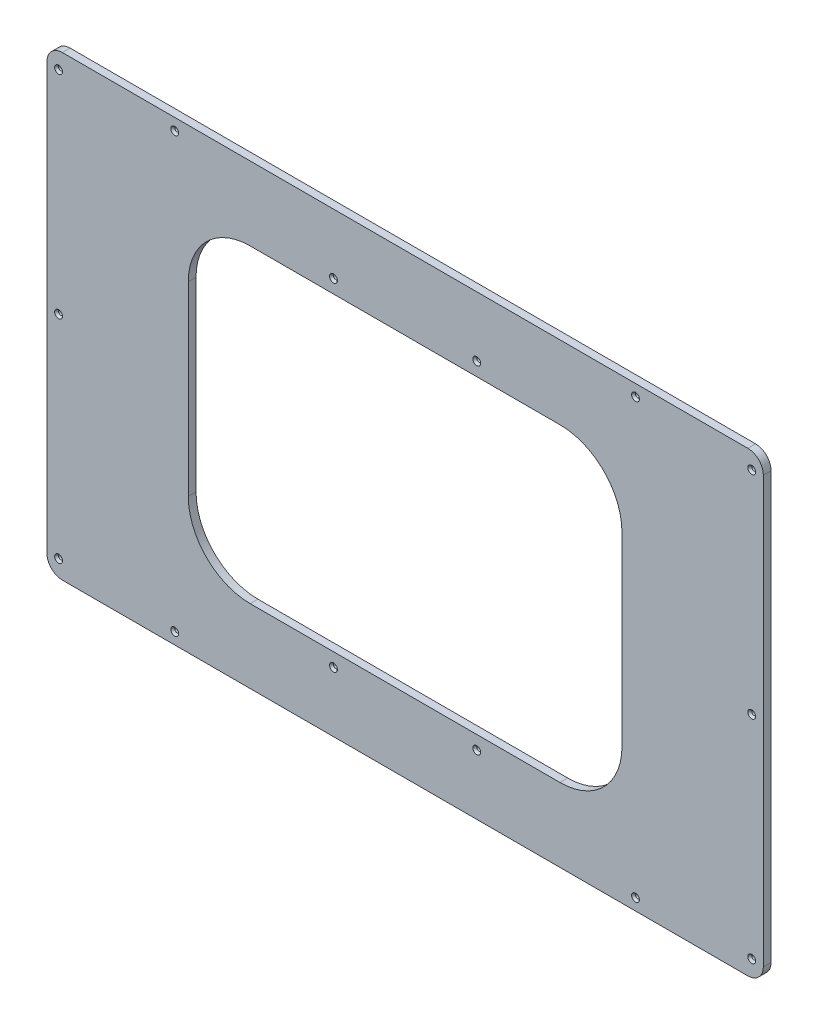
SolidWorks part; units mm, degrees
material "PE High Density"
ref_plane "Front Plane" through (0, 0, 0) normal (0, 0, 1) x (1, 0, 0)
ref_plane "Top Plane" through (0, 0, 0) normal (0, 1, 0) x (1, 0, 0)
ref_plane "Right Plane" through (0, 0, 0) normal (1, 0, 0) x (0, 0, -1)
sketch "Sketch1" plane through (0, 0, 0) normal (0, 0, 1) x (1, 0, 0)
  line L1 (-587.375, 374.65) -> (587.375, 374.65)
  line L2 (-587.375, 374.65) -> (-587.375, -374.65)
  line L3 (-587.375, -374.65) -> (587.375, -374.65)
  line L4 (587.375, 374.65) -> (587.375, -374.65)
  line L5 (-587.375, 374.65) -> (587.375, -374.65) construction
  line L6 (-587.375, -374.65) -> (587.375, 374.65) construction
  line L11 (-355.6, 254) -> (355.6, 254)
  line L12 (-355.6, 254) -> (-355.6, -254)
  line L13 (-355.6, -254) -> (355.6, -254)
  line L14 (355.6, 254) -> (355.6, -254)
  line L15 (-355.6, 254) -> (355.6, -254) construction
  line L16 (-355.6, -254) -> (355.6, 254) construction
  point P0 (0, 0)
  point P6 (0, 0)
  dimension "D1" = 231.775
  dimension "D2" = 749.3
  dimension "D3" = 508
  dimension "D4" = 711.2
extrude "Boss-Extrude1" add sketch "Sketch1" along normal blind 12.7
fillet "Fillet1" radius 101.6 4 edges at (355.6, 254, 6.35) (355.6, -254, 6.35) (-355.6, -254, 6.35) (-355.6, 254, 6.35)
hole_wizard "CSK for 1/4 Flat Head Machine Screw1" positions "Sketch4" profile "Sketch5" countersink size "1/4" standard "ANSI Inch" end condition through all
sketch "Sketch4" plane through (0, 0, 12.7) normal (0, 0, 1) x (1, 0, 0)
  line L0 (-587.375, -374.65) -> (587.375, -374.65) construction
  line L1 (-587.375, 374.65) -> (-587.375, -374.65) construction
  line L2 (587.375, 374.65) -> (-587.375, 374.65) construction
  line L3 (-587.375, 0) -> (587.375, 0) construction
  line L4 (587.375, -374.65) -> (587.375, 374.65) construction
  line L6 (0, 374.65) -> (0, -374.65) construction
  line L8 (-254, -254) -> (254, -254) construction
  point P0 (-568.325, -347.218)
  point P2 (-568.325, 0)
  point P27 (-377.825, 355.6)
  point P41 (-377.825, -355.6)
  point P42 (-568.325, 347.218)
  point P43 (377.825, -355.6)
  point P44 (568.325, -347.218)
  point P45 (568.325, 0)
  point P46 (568.325, 347.218)
  point P47 (377.825, 355.6)
  point P60 (-117.475, -276.225)
  point P65 (-117.475, 276.225)
  point P69 (117.475, 276.225)
  point P71 (117.475, -276.225)
  dimension "D1" = 347.218
  dimension "D2" = 27.432
  dimension "D3" = 209.55
  dimension "D4" = 19.05
  dimension "D5" = 19.05
  dimension "D7" = 22.225
  dimension "D8" = 117.475
sketch "Sketch5" plane through (-568.325, -347.218, 12.7) normal (1, 0, 0) x (0, -1, 0)
  line L0 (0, 0) -> (0, 12.7)
  line L1 (0, 12.7) -> (3.3782, 12.7)
  line L2 (3.3782, 12.7) -> (3.3782, 3.5209)
  line L3 (3.3782, 3.5209) -> (6.4389, 0)
  line L5 (6.4389, 0) -> (0, 0)
  line L6 (-3.3782, 3.5209) -> (-6.4389, 0) construction
  line L11 (0, -6.35) -> (0, 107.95) construction
  dimension "Thru Hole Dia." = 6.7564
  dimension "Thru Hole Depth" = 12.7
  dimension "Near C'Sink Dia." = 12.8778
  dimension "Near C'Sink Angle" = 82
fillet "Fillet2" radius 25.4 4 edges at (587.375, 374.65, 6.35) (587.375, -374.65, 6.35) (-587.375, -374.65, 6.35) (-587.375, 374.65, 6.35)
